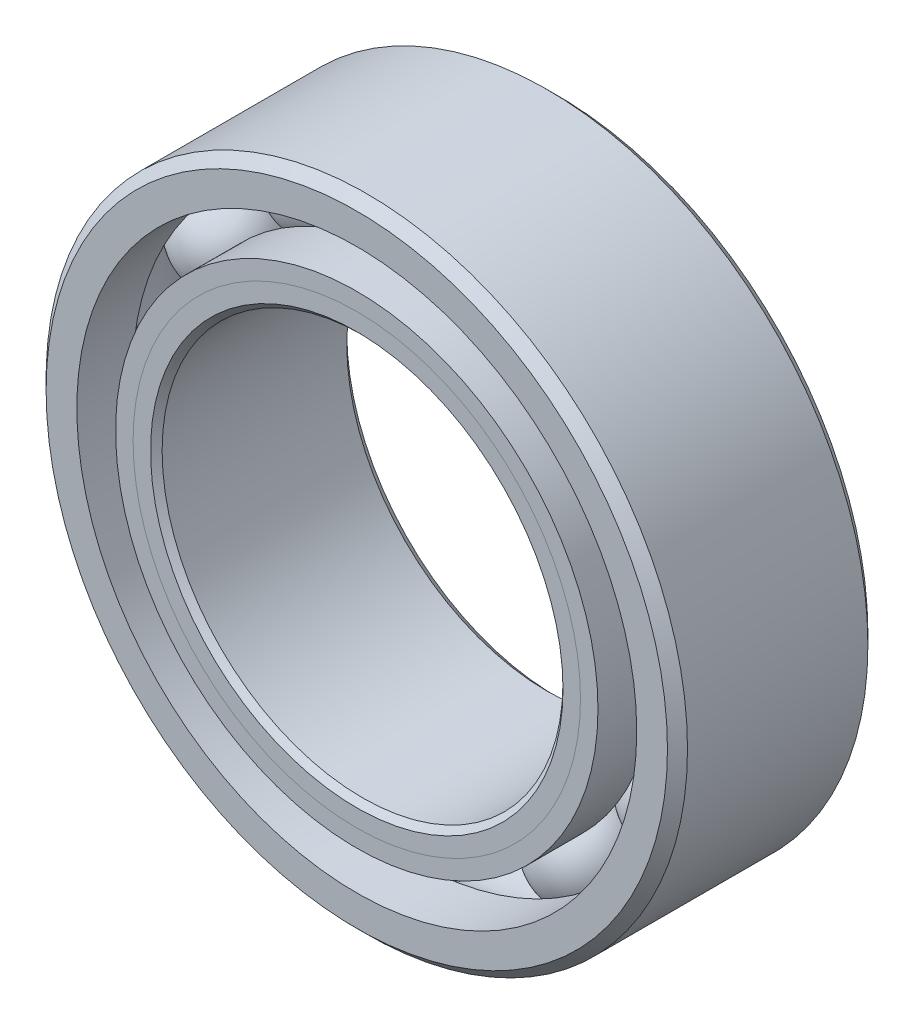
SolidWorks part; units mm, degrees
ref_plane "Front Plane" through (0, 0, 0) normal (0, 0, 1) x (1, 0, 0)
ref_plane "Top Plane" through (0, 0, 0) normal (0, 1, 0) x (1, 0, 0)
ref_plane "Right Plane" through (0, 0, 0) normal (1, 0, 0) x (0, 0, -1)
sketch "Sketch1" plane through (0, 0, 0) normal (1, 0, 0) x (0, 0, -1)
  line L0 (-1.9844, 0) -> (1.9844, 0) construction
  line L1 (0, 6.35) -> (0, -6.35) construction
  line L2 (1.7859, 6.35) -> (-1.7859, 6.35)
  line L3 (-1.7859, 6.35) -> (-1.9844, 6.1516)
  line L4 (-1.9844, 6.1516) -> (-1.9844, 5.5432)
  line L5 (-1.9844, 5.5432) -> (-0.8819, 5.5432)
  line L6 (1.9844, 5.5432) -> (0.8819, 5.5432)
  line L7 (1.9844, 6.1516) -> (1.9844, 5.5432)
  line L8 (1.7859, 6.35) -> (1.9844, 6.1516)
  line L9 (0, 6.35) -> (0, 5.1594) construction
  line L10 (0, 5.1594) -> (0, 3.9688) construction
  arc A0 (-0.8819, 5.5432) -> (0.8819, 5.5432) centre (0, 5.1594) cw
  point P14 (0, 3.9688)
  dimension "D3" = 1.7639
  dimension "D1" = 45
  dimension "Width" = 3.9688
  dimension "OD" = 12.7
  dimension "D2" = 0.1984
  dimension "Shaft Dia" = 7.9375
  dimension "D4" = 0.3838
revolve "Revolve1" add sketch "Sketch1" angle 360 about L0
sketch "Sketch2" plane through (0, 0, 0) normal (1, 0, 0) x (0, 0, -1)
  line L0 (-1.9844, 4.7756) -> (-0.8819, 4.7756)
  line L1 (-1.9844, 6.1516) -> (-1.9844, -6.1516) construction
  line L2 (-1.9844, 4.7756) -> (-1.9844, 4.4294)
  line L3 (-1.9844, 4.4294) -> (-1.6382, 4.0831)
  line L4 (-1.6382, 4.0831) -> (0, 4.0831)
  line L5 (0, 6.35) -> (0, -6.35) construction
  line L6 (0, 4.0831) -> (0, 4.1975)
  line L7 (0, 4.1975) -> (0, 3.9688) construction
  line L8 (-1.9844, 4.7756) -> (-1.9844, 4.0831) construction
  line L9 (-1.9844, 4.0831) -> (-1.6382, 4.0831) construction
  arc A0 (-0.8819, 4.7756) -> (0, 4.1975) centre (0, 5.1594) ccw
  arc A1 (0.8819, 5.5432) -> (-0.8819, 5.5432) centre (0, 5.1594) ccw construction
  circle A2 centre (0, 5.1594) radius 0.9618 construction
  dimension "D1" = 45
revolve "Revolve2" add sketch "Sketch2" angle 360 about L0
sketch "Sketch3" plane through (0, 0, 0) normal (1, 0, 0) x (0, 0, -1)
  line L0 (-1.9844, 4.4294) -> (-1.6382, 4.0831)
  line L1 (-1.6382, 4.0831) -> (0, 4.0831)
  line L2 (0, 4.0831) -> (0, 4.1975)
  line L3 (-1.9844, 4.4294) -> (-1.9844, 4.0831)
  line L4 (-1.9844, 4.7756) -> (-1.9844, 4.0831) construction
  line L5 (-1.9844, 4.0831) -> (-1.87, 3.9688)
  line L6 (-1.87, 3.9688) -> (1.7859, 3.9688)
  line L7 (1.7859, 6.35) -> (1.7859, -6.35) construction
  line L8 (1.7859, 3.9688) -> (1.9844, 4.1672)
  line L9 (1.9844, -6.1516) -> (1.9844, 6.1516) construction
  line L10 (1.9844, 4.1672) -> (1.9844, 4.7756)
  line L11 (1.9844, 4.7756) -> (0.8819, 4.7756)
  line L13 (1.7859, 6.35) -> (1.9844, 6.1516) construction
  circle A0 centre (0, 5.1594) radius 0.9618 construction
  arc A1 (0.8819, 4.7756) -> (0, 4.1975) centre (0, 5.1594) cw
revolve "Revolve3" add sketch "Sketch3" angle 360 about L0
sketch "Sketch4" plane through (0, 0, 0) normal (1, 0, 0) x (0, 0, -1)
  line L0 (-0.9618, 5.1594) -> (0.9618, 5.1594)
  circle A1 centre (0, 5.1594) radius 0.9618 construction
  arc A2 (-0.9618, 5.1594) -> (0.9618, 5.1594) centre (0, 5.1594) cw
  arc A3 (0.8819, 5.5432) -> (-0.8819, 5.5432) centre (0, 5.1594) ccw construction
revolve "Revolve4" add sketch "Sketch4" angle 360 about L0
ref_axis "Axis1" through (0, 0, -1.9844) along (0, 0, 1)
pattern_circular "CirPattern1" count 12 every 30 about axis through (0, 0, -1.9844) along (0, 0, 1) of bodies 104
equation "\"D2@Sketch1\" = \"Width@Sketch1\"*.05"
equation "\"D3@Sketch1\" = \"Width@Sketch1\"/2.25"
equation "\"D4@Sketch1\" = (((\"OD@Sketch1\"-\"Width@Sketch1\")/2)/3.25)/3.5"
equation "\"D2@CirPattern1\" = 360/\"Balls@CirPattern1\""
